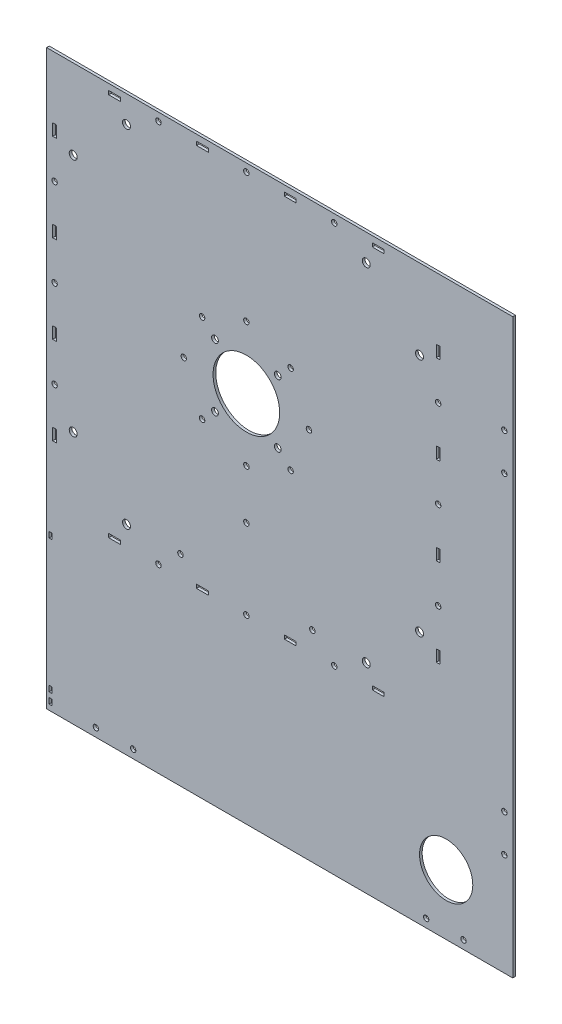
SolidWorks part; units mm, degrees
ref_plane "前视基准面" through (0, 0, 0) normal (0, 0, 1) x (1, 0, 0)
ref_plane "上视基准面" through (0, 0, 0) normal (0, 1, 0) x (1, 0, 0)
ref_plane "右视基准面" through (0, 0, 0) normal (1, 0, 0) x (0, 0, -1)
sketch "草图1" plane through (0, 0, 0) normal (0, 0, 1) x (1, 0, 0)
  line L0 (1.4571, -21.1871) -> (1.4571, -41.1871) construction
  line L2 (1.4571, -21.1871) -> (1.4571, 44.8129) construction
  line L4 (151.4571, -41.1871) -> (151.4571, 108.8129)
  line L5 (151.4571, 108.8129) -> (-148.5429, 108.8129)
  line L6 (-148.5429, 108.8129) -> (-148.5429, -191.1871)
  line L7 (-148.5429, -191.1871) -> (151.4571, -191.1871)
  line L8 (151.4571, -191.1871) -> (151.4571, -41.1871)
  line L9 (-148.5429, -41.1871) -> (-161.9412, -41.1871) construction
  line L10 (1.4571, -191.1871) -> (1.4571, -181.0361) construction
  circle A6 centre (1.4571, -21.1871) radius 241.4173 construction
  circle A9 centre (1.4571, -41.1871) radius 25
  circle A10 centre (25.0271, -17.6171) radius 2.55
  circle A11 centre (25.0271, -64.7571) radius 2.55
  circle A12 centre (-22.1129, -64.7571) radius 2.55
  circle A13 centre (-22.1129, -17.6171) radius 2.55
  circle A14 centre (115.1844, -53.0393) radius 12.2821 construction
  dimension "D1" = 50
  dimension "D4" = 5.1
  dimension "D2" = 300
  dimension "D3" = 300
  dimension "D5" = 23.57
  dimension "D6" = 23.57
  dimension "D7" = 4
extrude "凸台-拉伸1" add sketch "草图1" along normal blind 2
sketch "草图3" plane through (0, 0, 2) normal (0, 0, 1) x (1, 0, 0)
  line L1 (96.0571, -183.7871) -> (104.8571, -183.7871)
  line L13 (1.4571, -191.1871) -> (1.4571, -185.1871) construction
  line L14 (-148.5429, -191.1871) -> (151.4571, -191.1871) construction
  line L15 (1.4571, -185.1871) -> (34.4571, -185.1871) construction
  line L16 (34.4571, -185.1871) -> (67.4571, -185.1871) construction
  line L17 (30.0571, -183.7871) -> (38.8571, -183.7871)
  line L18 (30.0571, -183.7871) -> (30.0571, -186.5871)
  line L19 (30.0571, -186.5871) -> (38.8571, -186.5871)
  line L20 (38.8571, -183.7871) -> (38.8571, -186.5871)
  line L21 (30.0571, -183.7871) -> (38.8571, -186.5871) construction
  line L22 (30.0571, -186.5871) -> (38.8571, -183.7871) construction
  line L23 (67.4571, -185.1871) -> (100.4571, -185.1871) construction
  line L24 (96.0571, -183.7871) -> (96.0571, -186.5871)
  line L25 (96.0571, -186.5871) -> (104.8571, -186.5871)
  line L26 (96.0571, -186.5871) -> (104.8571, -183.7871) construction
  line L27 (104.8571, -186.5871) -> (104.8571, -183.7871)
  line L28 (-35.9429, -183.7871) -> (-35.9429, -186.5871)
  line L29 (-27.1429, -183.7871) -> (-35.9429, -183.7871)
  line L30 (-27.1429, -183.7871) -> (-27.1429, -186.5871)
  line L31 (-27.1429, -186.5871) -> (-35.9429, -186.5871)
  line L32 (-93.1429, -183.7871) -> (-93.1429, -186.5871)
  line L33 (-101.9429, -186.5871) -> (-101.9429, -183.7871)
  line L34 (-93.1429, -183.7871) -> (-101.9429, -183.7871)
  line L35 (-93.1429, -186.5871) -> (-101.9429, -186.5871)
  line L36 (-141.1429, 53.4129) -> (-141.1429, 62.2129)
  line L37 (-143.9429, 53.4129) -> (-143.9429, 62.2129)
  line L38 (-143.9429, 62.2129) -> (-141.1429, 62.2129)
  line L39 (-141.1429, 53.4129) -> (-143.9429, 53.4129)
  line L40 (-141.1429, -12.5871) -> (-141.1429, -3.7871)
  line L41 (-141.1429, -3.7871) -> (-143.9429, -3.7871)
  line L42 (-143.9429, -12.5871) -> (-143.9429, -3.7871)
  line L43 (-141.1429, -12.5871) -> (-143.9429, -12.5871)
  line L44 (-141.1429, -69.7871) -> (-143.9429, -69.7871)
  line L45 (-141.1429, -69.7871) -> (-141.1429, -78.5871)
  line L46 (-143.9429, -69.7871) -> (-143.9429, -78.5871)
  line L47 (-141.1429, -78.5871) -> (-143.9429, -78.5871)
  line L48 (-141.1429, -135.7871) -> (-141.1429, -144.5871)
  line L49 (-143.9429, -135.7871) -> (-143.9429, -144.5871)
  line L50 (-141.1429, -135.7871) -> (-143.9429, -135.7871)
  line L51 (-143.9429, -144.5871) -> (-141.1429, -144.5871)
  line L52 (96.0571, 101.4129) -> (104.8571, 101.4129)
  line L53 (96.0571, 104.2129) -> (104.8571, 104.2129)
  line L54 (104.8571, 104.2129) -> (104.8571, 101.4129)
  line L55 (96.0571, 101.4129) -> (96.0571, 104.2129)
  line L56 (30.0571, 101.4129) -> (38.8571, 101.4129)
  line L57 (38.8571, 101.4129) -> (38.8571, 104.2129)
  line L58 (30.0571, 104.2129) -> (38.8571, 104.2129)
  line L59 (30.0571, 101.4129) -> (30.0571, 104.2129)
  line L60 (-27.1429, 101.4129) -> (-27.1429, 104.2129)
  line L61 (-27.1429, 101.4129) -> (-35.9429, 101.4129)
  line L62 (-27.1429, 104.2129) -> (-35.9429, 104.2129)
  line L63 (-35.9429, 101.4129) -> (-35.9429, 104.2129)
  line L64 (-93.1429, 101.4129) -> (-101.9429, 101.4129)
  line L65 (-93.1429, 104.2129) -> (-101.9429, 104.2129)
  line L66 (-93.1429, 101.4129) -> (-93.1429, 104.2129)
  line L67 (-101.9429, 104.2129) -> (-101.9429, 101.4129)
  line L68 (144.0571, -135.7871) -> (144.0571, -144.5871)
  line L69 (146.8571, -135.7871) -> (146.8571, -144.5871)
  line L70 (146.8571, -144.5871) -> (144.0571, -144.5871)
  line L71 (144.0571, -135.7871) -> (146.8571, -135.7871)
  line L72 (144.0571, -69.7871) -> (144.0571, -78.5871)
  line L73 (144.0571, -78.5871) -> (146.8571, -78.5871)
  line L74 (146.8571, -69.7871) -> (146.8571, -78.5871)
  line L75 (144.0571, -69.7871) -> (146.8571, -69.7871)
  line L76 (144.0571, -12.5871) -> (146.8571, -12.5871)
  line L77 (144.0571, -12.5871) -> (144.0571, -3.7871)
  line L78 (146.8571, -12.5871) -> (146.8571, -3.7871)
  line L79 (144.0571, -3.7871) -> (146.8571, -3.7871)
  line L80 (144.0571, 53.4129) -> (144.0571, 62.2129)
  line L81 (146.8571, 53.4129) -> (146.8571, 62.2129)
  line L82 (144.0571, 53.4129) -> (146.8571, 53.4129)
  line L83 (146.8571, 62.2129) -> (144.0571, 62.2129)
  line L84 (50.9571, -185.1871) -> (50.9571, -170.1871) construction
  line L85 (17.9571, -185.1871) -> (17.9571, -170.1871) construction
  line L86 (-48.0429, -170.1871) -> (-15.0429, -170.1871) construction
  line L91 (-31.5429, -170.1871) -> (-31.5429, -155.1871) construction
  line L92 (100.4571, -185.1871) -> (104.8571, -186.5871) construction
  line L93 (-31.5429, -155.1871) -> (1.4571, -155.1871) construction
  line L95 (1.4571, -155.1871) -> (34.4571, -155.1871) construction
  circle A0 centre (1.4571, -185.1871) radius 2.05
  circle A1 centre (67.4571, -185.1871) radius 2.05
  circle A2 centre (-64.5429, -185.1871) radius 2.05
  circle A3 centre (-142.5429, 24.8129) radius 2.05
  circle A4 centre (-142.5429, -41.1871) radius 2.05
  circle A5 centre (-142.5429, -107.1871) radius 2.05
  circle A6 centre (67.4571, 102.8129) radius 2.05
  circle A7 centre (1.4571, 102.8129) radius 2.05
  circle A8 centre (-64.5429, 102.8129) radius 2.05
  circle A9 centre (145.4571, -107.1871) radius 2.05
  circle A10 centre (145.4571, -41.1871) radius 2.05
  circle A11 centre (145.4571, 24.8129) radius 2.05
  circle A15 centre (17.9571, -170.1871) radius 2 construction
  circle A16 centre (-15.0429, -170.1871) radius 2 construction
  circle A17 centre (50.9571, -170.1871) radius 2.05
  circle A18 centre (-48.0429, -170.1871) radius 2.05
  circle A19 centre (-31.5429, -155.1871) radius 2.05 construction
  circle A20 centre (34.4571, -155.1871) radius 2.05 construction
  circle A22 centre (1.4571, -155.1871) radius 2 construction
  circle A23 centre (1.4571, -41.1871) radius 47 construction
  circle A24 centre (1.4571, -88.1871) radius 2.05
  circle A25 centre (-31.7769, -74.4212) radius 2.05
  circle A26 centre (-45.5429, -41.1871) radius 2.05
  circle A27 centre (-31.7769, -7.9531) radius 2.05
  circle A28 centre (1.4571, 5.8129) radius 2.05
  circle A29 centre (34.6912, -7.9531) radius 2.05
  circle A30 centre (48.4571, -41.1871) radius 2.05
  circle A31 centre (34.6912, -74.4212) radius 2.05
  circle A32 centre (1.4571, -125.1871) radius 2.05
  dimension "D1" = 8.8
  dimension "D3" = 4
  dimension "D4" = 8
  dimension "D5" = 30
  dimension "D6" = 4.1
  dimension "D7" = 94
  dimension "D8" = 4.1
  dimension "D9" = 8.8
  dimension "D2" = 2.8
  dimension "D10" = 2.8
extrude "切除-拉伸2" cut sketch "草图3" against normal blind 4
sketch "草图6" plane through (0, 0, 2) normal (0, 0, 1) x (1, 0, 0)
sketch "草图7" plane through (0, 0, 2) normal (0, 0, 1) x (1, 0, 0)
  line L5 (-148.5429, -171.1871) -> (151.4571, -171.1871) construction
  line L6 (-148.5429, 108.8129) -> (-148.5429, -191.1871) construction
  line L7 (151.4571, -191.1871) -> (151.4571, 108.8129) construction
  line L8 (-148.5429, -191.1871) -> (151.4571, -191.1871) construction
  circle A0 centre (-88.5429, -171.1871) radius 3
  circle A1 centre (91.4571, -171.1871) radius 3
  circle A2 centre (-128.5429, 48.8129) radius 3
  circle A3 centre (-128.5429, -131.1871) radius 3
  circle A4 centre (91.4571, 88.8129) radius 3
  circle A5 centre (-88.5429, 88.8129) radius 3
  circle A6 centre (131.4571, -131.1871) radius 3
  circle A7 centre (131.4571, 48.8129) radius 3
  dimension "D2" = 6
  dimension "D4" = 60
  dimension "D1" = 20
  dimension "D3" = 60
  dimension "D5" = 4
extrude "切除-拉伸3" cut sketch "草图7" against normal blind 10
sketch "草图9" plane through (0, 0, 2) normal (0, 0, 1) x (1, 0, 0)
  line L0 (151.4571, 108.8129) -> (201.4571, 108.8129)
  line L1 (151.4571, -191.1871) -> (201.4571, -191.1871) construction
  line L2 (201.4571, -191.1871) -> (201.4571, 108.8129)
  line L3 (151.4571, 108.8129) -> (151.4571, -191.1871)
  line L6 (201.4571, -321.1871) -> (201.4571, -191.1871)
  line L7 (-148.5429, -191.1871) -> (151.4571, -191.1871)
  line L11 (201.4571, -323.3871) -> (203.6571, -321.1871) construction
  line L12 (201.4571, -321.1871) -> (203.6571, -321.1871) construction
  line L13 (201.4571, -321.1871) -> (201.4571, -323.3871) construction
  line L14 (201.4571, -323.3871) -> (203.6571, -323.3871) construction
  line L15 (203.6571, -321.1871) -> (203.6571, -323.3871) construction
  line L16 (-150.7429, -323.3871) -> (-148.5429, -321.1871) construction
  line L17 (-148.5429, -321.1871) -> (-150.7429, -321.1871) construction
  line L18 (-148.5429, -321.1871) -> (-148.5429, -323.3871) construction
  line L19 (-148.5429, -323.3871) -> (-150.7429, -323.3871) construction
  line L20 (-150.7429, -321.1871) -> (-150.7429, -323.3871) construction
  line L21 (-146.7429, -315.0371) -> (-144.4429, -315.0371) construction
  line L22 (-144.4429, -317.1871) -> (-146.7429, -317.1871)
  line L23 (-144.4429, -317.1871) -> (-144.4429, -312.8871)
  line L24 (-144.4429, -312.8871) -> (-146.7429, -312.8871)
  line L25 (-146.7429, -317.1871) -> (-146.7429, -312.8871)
  line L26 (-144.4429, -309.1871) -> (-146.7429, -309.1871)
  line L27 (-144.4429, -309.1871) -> (-144.4429, -304.8871)
  line L28 (-144.4429, -304.8871) -> (-146.7429, -304.8871)
  line L29 (-146.7429, -309.1871) -> (-146.7429, -304.8871)
  line L30 (-146.7429, -307.0371) -> (-144.4429, -307.0371) construction
  line L31 (-148.5429, -321.1871) -> (201.4571, -321.1871)
  line L32 (-148.5429, -321.1871) -> (-148.5429, -191.1871)
  line L33 (-111.5429, -314.8871) -> (-83.5429, -314.8871) construction
  line L34 (-144.4429, -204.8871) -> (-146.7429, -204.8871)
  line L35 (-144.4429, -204.8871) -> (-144.4429, -209.1871)
  line L36 (-144.4429, -209.1871) -> (-146.7429, -209.1871)
  line L37 (-146.7429, -204.8871) -> (-146.7429, -209.1871)
  line L38 (26.4571, -321.1871) -> (26.4571, -291.6065) construction
  line L39 (182.6983, -321.1871) -> (182.6983, 108.8129) construction
  line L40 (182.6983, -106.1871) -> (169.8123, -106.1871) construction
  line L41 (195.1571, -244.1871) -> (195.1571, -216.1871) construction
  line L42 (-146.7429, -207.0371) -> (-144.4429, -207.0371) construction
  arc A1 (-148.5429, -303.223) -> (-130.5787, -321.1871) centre (-148.5429, -321.1871) ccw construction
  circle A2 centre (202.5571, -322.2871) radius 1.5556 construction
  circle A3 centre (-149.6429, -322.2871) radius 1.5556 construction
  circle A4 centre (151.4571, -275.7999) radius 20
  circle A5 centre (-111.5429, -314.8871) radius 2
  circle A6 centre (-83.5429, -314.8871) radius 2
  circle A7 centre (136.4571, -314.8871) radius 2
  circle A8 centre (164.4571, -314.8871) radius 2
  circle A9 centre (195.1571, -244.1871) radius 2
  circle A10 centre (195.1571, -216.1871) radius 2
  circle A11 centre (195.1571, 3.8129) radius 2
  circle A12 centre (195.1571, 31.8129) radius 2
  point P32 (-149.6429, -321.1871)
  point P65 (-145.5929, -207.0371)
  dimension "D12" = 4.3
  dimension "D13" = 28
  dimension "D14" = 4
  dimension "D15" = 4
  dimension "D18" = 4
  dimension "D20" = 4
  dimension "D1" = 50
  dimension "D2" = 130
  dimension "D3" = 2.2
  dimension "D4" = 2.2
  dimension "D5" = 2.2
  dimension "D6" = 4.3
  dimension "D7" = 4.3
  dimension "D8" = 4
  dimension "D9" = 8
  dimension "D10" = 2.3
  dimension "D11" = 2.3
  dimension "D16" = 6.3
  dimension "D17" = 220
  dimension "D19" = 28
  dimension "D21" = 6.3
  dimension "D22" = 220
  dimension "D23" = 100
  dimension "D24" = 2.3
extrude "凸台-拉伸3" add sketch "草图9" against normal blind 2
